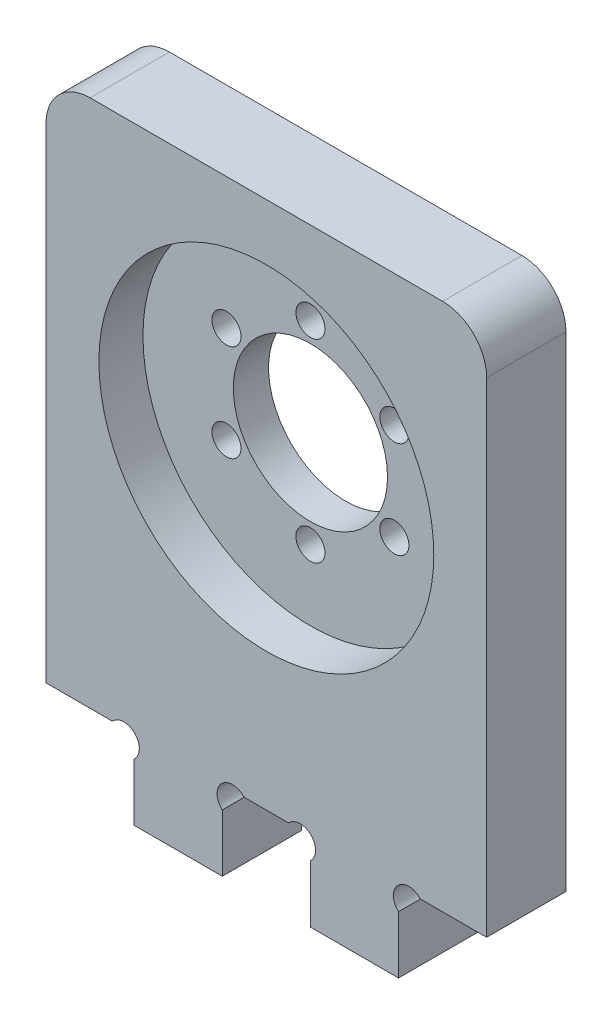
SolidWorks part; units mm, degrees
ref_plane "Plan de face" through (0, 0, 0) normal (0, 0, 1) x (1, 0, 0)
ref_plane "Plan de dessus" through (0, 0, 0) normal (0, 1, 0) x (1, 0, 0)
ref_plane "Plan de droite" through (0, 0, 0) normal (1, 0, 0) x (0, 0, -1)
sketch "Esquisse1" plane through (0, 0, 0) normal (0, 0, 1) x (1, 0, 0)
  line L1 (0, 0) -> (50, 0)
  line L2 (0, 0) -> (0, 60)
  line L3 (0, 60) -> (50, 60)
  line L4 (50, 0) -> (50, 60)
  dimension "D1" = 50
  dimension "D2" = 60
extrude "Boss.-Extru.1" add sketch "Esquisse1" along normal blind 9
sketch "Esquisse2" plane through (0, 0, 9) normal (0, 0, 1) x (1, 0, 0)
  line L0 (0, 0) -> (50, 0) construction
  line L1 (30, 0) -> (40, 0)
  line L2 (30, 0) -> (30, -9)
  line L3 (30, -9) -> (40, -9)
  line L4 (40, 0) -> (40, -9)
  line L5 (35, 0.8798) -> (35, -9) construction
  line L6 (25, 0) -> (25, -9) construction
  line L7 (15, 0.8798) -> (15, -9) construction
  line L8 (10, 0) -> (10, -9)
  line L9 (20, -9) -> (10, -9)
  line L10 (20, 0) -> (20, -9)
  line L11 (20, 0) -> (10, 0)
  dimension "D1" = 9
  dimension "D2" = 5
  dimension "D3" = 10
extrude "Boss.-Extru.2" add sketch "Esquisse2" against normal up to vertex (9 mm away) up to point (50, 60, 0)
sketch "Esquisse3" plane through (0, 0, 9) normal (0, 0, 1) x (1, 0, 0)
  line L0 (25, 60) -> (25, 34.6) construction
  line L1 (50, 60) -> (0, 60) construction
  line L2 (20, 0) -> (30, 0) construction
  circle A0 centre (25, 34.6) radius 8.75
  circle A1 centre (25, 45.6) radius 1.65
  circle A2 centre (34.5263, 40.1) radius 1.65
  circle A3 centre (34.5263, 29.1) radius 1.65
  circle A4 centre (25, 23.6) radius 1.65
  circle A5 centre (15.4737, 29.1) radius 1.65
  circle A6 centre (15.4737, 40.1) radius 1.65
  point P21 (25, 34.6)
  dimension "D1" = 17.5
  dimension "D3" = 11
  dimension "D4" = 3.3
  dimension "D2" = 34.6
  dimension "D5" = 6
extrude "Enlèv. mat.-Extru.1" cut sketch "Esquisse3" against normal up to vertex (9 mm away) up to point (0, 60, 0)
sketch "Esquisse4" plane through (0, 0, 9) normal (0, 0, 1) x (1, 0, 0)
  circle A0 centre (25, 34.6) radius 19
  dimension "D1" = 38
extrude "Enlèv. mat.-Extru.2" cut sketch "Esquisse4" against normal blind 5
fillet "Congé1" radius 5 2 edges at (50, 60, 4.5) (0, 60, 4.5)
sketch "Esquisse5" plane through (0, 0, 9) normal (0, 0, 1) x (1, 0, 0)
  line L0 (25, 0) -> (25, -8.4272) construction
  line L1 (20, 0) -> (30, 0) construction
  line L2 (30, 0) -> (30, -9) construction
  line L3 (27.5251, 0) -> (30, -2.4749)
  line L4 (28.7626, -1.2374) -> (28.8314, -1.1686) construction
  line L5 (28.8314, -1.1686) -> (30, 0) construction
  line L6 (30, 0) -> (30.0707, 0.0707) construction
  line L7 (20, 0) -> (19.9293, 0.0707) construction
  line L8 (21.1686, -1.1686) -> (20, 0) construction
  line L9 (21.2374, -1.2374) -> (21.1686, -1.1686) construction
  line L10 (22.4749, 0) -> (20, -2.4749)
  line L11 (35, -9) -> (35, -3.156) construction
  line L12 (30, -9) -> (40, -9) construction
  line L13 (40, 0) -> (39.9293, 0.0707) construction
  line L14 (41.1686, -1.1686) -> (40, 0) construction
  line L15 (41.2374, -1.2374) -> (41.1686, -1.1686) construction
  line L16 (42.4749, 0) -> (40, -2.4749)
  line L17 (30, 0) -> (30.0707, 0.0707) construction
  line L18 (8.7626, -1.2374) -> (8.8314, -1.1686) construction
  line L19 (8.8314, -1.1686) -> (10, 0) construction
  line L20 (10, 0) -> (10.0707, 0.0707) construction
  line L21 (7.5251, 0) -> (10, -2.4749)
  arc A0 (27.5251, 0) -> (30, -2.4749) centre (28.8314, -1.1686) cw
  arc A1 (22.4749, 0) -> (20, -2.4749) centre (21.1686, -1.1686) ccw
  arc A2 (42.4749, 0) -> (40, -2.4749) centre (41.1686, -1.1686) ccw
  arc A3 (7.5251, 0) -> (10, -2.4749) centre (8.8314, -1.1686) cw
  dimension "D1" = 3.5
  dimension "D2" = 0.1
extrude "Enlèv. mat.-Extru.3" cut sketch "Esquisse5" against normal through all both and the other way through all
